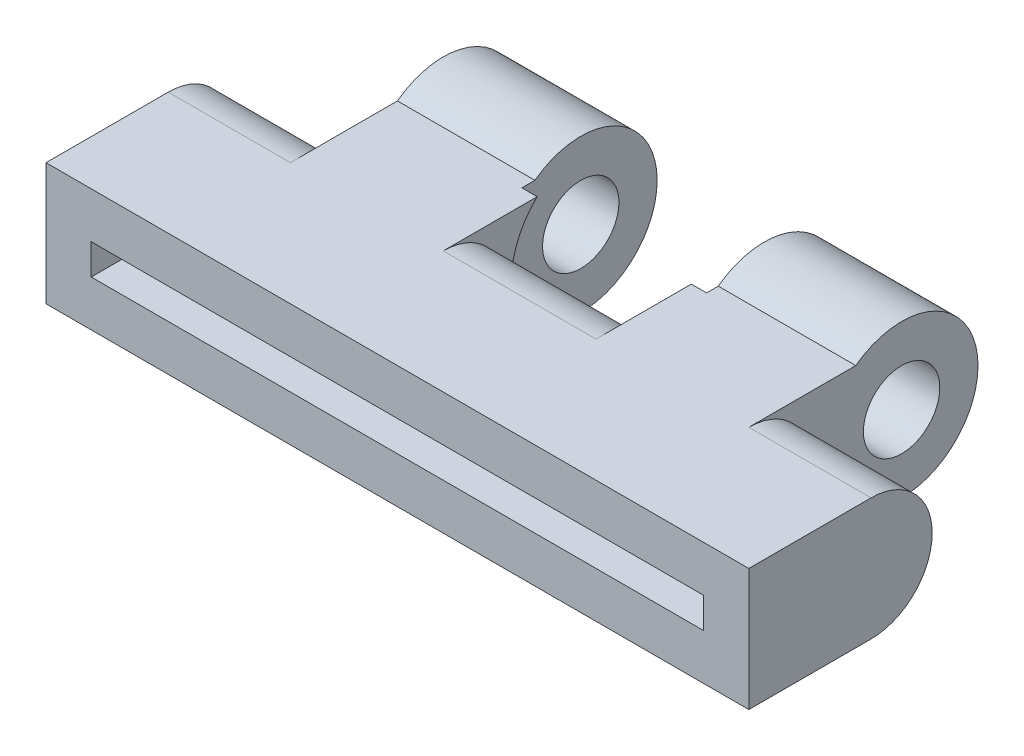
SolidWorks part; units mm, degrees
ref_plane "Front Plane" through (0, 0, 0) normal (0, 0, 1) x (1, 0, 0)
ref_plane "Top Plane" through (0, 0, 0) normal (0, 1, 0) x (1, 0, 0)
ref_plane "Right Plane" through (0, 0, 0) normal (1, 0, 0) x (0, 0, -1)
sketch "Sketch2" plane through (0, 0, 0) normal (0, 0, 1) x (1, 0, 0)
  line L1 (0, 0) -> (230, 0)
  line L2 (0, 0) -> (0, 40)
  line L3 (0, 40) -> (230, 40)
  line L4 (230, 0) -> (230, 40)
extrude "Boss-Extrude1" add sketch "Sketch2" along normal blind 80
sketch "Sketch3" plane through (0, 0, 80) normal (0, 0, 1) x (1, 0, 0)
  line L1 (14.8, 25) -> (215.2, 25)
  line L2 (14.8, 25) -> (14.8, 15)
  line L3 (14.8, 15) -> (215.2, 15)
  line L4 (215.2, 25) -> (215.2, 15)
  line L5 (14.8, 25) -> (215.2, 15) construction
  line L6 (14.8, 15) -> (215.2, 25) construction
  point P0 (115, 20)
extrude "Cut-Extrude1" cut sketch "Sketch3" against normal blind 30
ref_plane "Plane1" through (115, 0, 0) normal (1, 0, 0) x (0, 0, -1)
ref_plane "Plane2" through (140, 0, 0) normal (1, 0, 0) x (0, 0, -1)
sketch "Sketch6" plane through (140, 0, 0) normal (1, 0, 0) x (0, 0, -1)
  circle A0 centre (10, 20) radius 25
extrude "Boss-Extrude3" add sketch "Sketch6" along normal blind 50 contours A0
sketch "Sketch7" plane through (140, 0, 0) normal (-1, 0, 0) x (0, 0, 1)
  circle A0 centre (-10, 20) radius 12.5
extrude "Cut-Extrude2" cut sketch "Sketch7" against normal blind 50
sketch "Sketch8" plane through (140, 0, 0) normal (-1, 0, 0) x (0, 0, 1)
  circle A0 centre (-10, 20) radius 26.5
extrude "Cut-Extrude3" cut sketch "Sketch8" along normal blind 25
sketch "Sketch11" plane through (190, 0, 0) normal (1, 0, 0) x (0, 0, -1)
  circle A0 centre (10, 20) radius 26.5
extrude "Cut-Extrude4" cut sketch "Sketch11" along normal blind 40
mirror "Mirror1" about plane through (115, 0, 0) normal (1, 0, 0) of "Cut-Extrude4", "Cut-Extrude3", "Cut-Extrude2", "Boss-Extrude3"
sketch "Sketch12" plane through (230, 0, 0) normal (1, 0, 0) x (0, 0, -1)
  line L0 (-80, 0) -> (-80, 40) construction
  line L1 (-80, 20) -> (-16.4749, 20)
  line L2 (-80, 20) -> (-80, 0)
  line L3 (-80, 0) -> (-16.4749, 0)
  line L4 (-16.4749, 20) -> (-16.4749, 0)
  line L5 (-80, 0) -> (-7.3853, 0) construction
ref_plane "Plane3" through (65, 0, 0) normal (1, 0, 0) x (0, 0, -1)
ref_plane "Plane4" through (165, 0, 0) normal (-1, 0, 0) x (0, 0, 1)
sketch "Sketch14" plane through (90, 0, 0) normal (1, 0, 0) x (0, 0, -1)
  line L0 (-80, 0) -> (-16.4749, 0) construction
  line L1 (-7.3853, 40) -> (-20, 40)
  line L2 (-7.3853, 40) -> (-7.3853, 0)
  line L3 (-7.3853, 0) -> (-20, 0)
  line L4 (-20, 40) -> (-20, 0)
extrude "Cut-Extrude6" cut sketch "Sketch14" along normal blind 50
fillet "Fillet3" radius 20 2 edges at (115, 40, 20) (115, 0, 20)
mirror "Mirror5" about plane through (165, 0, 0) normal (-1, 0, 0) of "Cut-Extrude6", "Fillet3"
mirror "Mirror8" about plane through (65, 0, 0) normal (1, 0, 0) of "Fillet3", "Cut-Extrude6"
sketch "Sketch15" plane through (90, 0, 0) normal (1, 0, 0) x (0, 0, -1)
  circle A0 centre (10, 20) radius 27.7712
extrude "Cut-Extrude7" cut sketch "Sketch15" against normal blind 5
sketch "Sketch17" plane through (65, 0, 0) normal (1, 0, 0) x (0, 0, -1)
  circle A0 centre (9.9276, 20.0671) radius 27.2335
  point P2 (0, 0)
  point P3 (256.86, 35.1867)
sketch "Sketch20" plane through (65, 0, 0) normal (1, 0, 0) x (0, 0, -1)
  circle A0 centre (10.3299, 20.0671) radius 27.6358
sketch "Sketch21" plane through (140, 0, 0) normal (-1, 0, 0) x (0, 0, 1)
  circle A0 centre (-10.3299, 20.0671) radius 27.6358
extrude "Cut-Extrude8" cut sketch "Sketch21" against normal blind 5 contours A0
